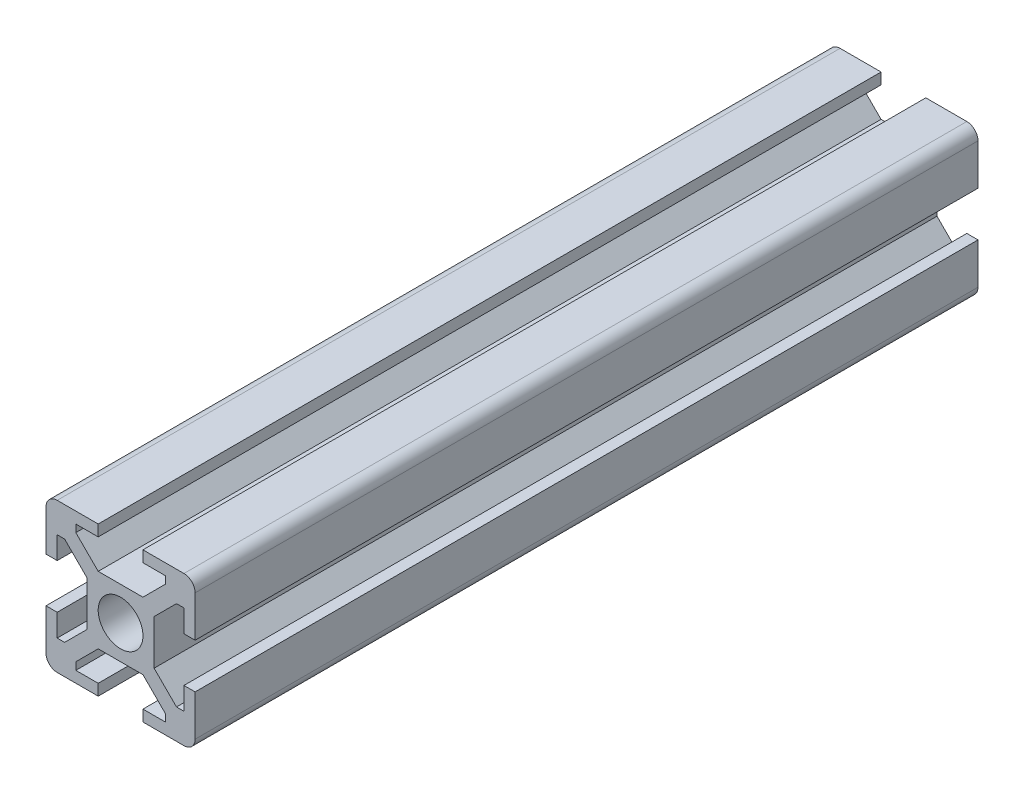
SolidWorks part; units mm, degrees
ref_plane "Plan de face" through (0, 0, 0) normal (0, 0, 1) x (1, 0, 0)
ref_plane "Plan de dessus" through (0, 0, 0) normal (0, 1, 0) x (1, 0, 0)
ref_plane "Plan de droite" through (0, 0, 0) normal (1, 0, 0) x (0, 0, -1)
sketch "Esquisse1" plane through (0, 0, 0) normal (0, 0, 1) x (1, 0, 0)
  line L0 (-10, 10) -> (10, -10) construction
  line L1 (-10, 10) -> (10, 10)
  line L2 (-10, 10) -> (-10, -10)
  line L3 (-10, -10) -> (10, -10)
  line L4 (10, 10) -> (10, -10)
  dimension "D1" = 20
extrude "Extrusion1" add sketch "Esquisse1" along normal mid plane 105
fillet "Congé1" radius 1.5 4 edges at (-10, -10, 0) (10, -10, 0) (-10, 10, 0) (10, 10, 0)
sketch "Esquisse2" plane through (0, 0, -52.5) normal (0, 0, -1) x (-1, 0, 0)
  line L0 (-10, 3) -> (-10, -3)
  line L1 (-10, -8.5) -> (-10, 8.5) construction
  line L2 (-10, -3) -> (-8.5, -3)
  line L3 (-8.5, -3) -> (-8.5, -6)
  line L4 (-8.5, 6) -> (-7.5, 6)
  line L5 (-4.5, -3) -> (-4.5, 3)
  line L6 (-7.5, 6) -> (-4.5, 3)
  line L7 (-8.5, 6) -> (-8.5, 3)
  line L8 (-8.5, 3) -> (-10, 3)
  line L9 (0, 0) -> (-10, 0) construction
  line L10 (-8.5, -6) -> (-7.5, -6)
  line L11 (-7.5, -6) -> (-4.5, -3)
  point P4 (-10, 0)
  dimension "D1" = 6
  dimension "D2" = 12
  dimension "D3" = 1.5
  dimension "D4" = 5.5
  dimension "D5" = 135
extrude "Enlèv. mat.-Extru.1" cut sketch "Esquisse2" against normal through all
ref_axis "Axe1" through (0, 0, 9.3338) along (0, 0, -1)
pattern_circular "Répétition circulaire1" count 4 over 360 about axis through (0, 0, 9.3338) along (0, 0, -1) of "Enlèv. mat.-Extru.1"
hole_wizard "Trou taraudé M6x1.01" positions "Esquisse4" profile "Esquisse5" tap size "M6x1.0" standard "Ansi Métrique"
sketch "Esquisse4" plane through (0, 0, -52.5) normal (0, 0, -1) x (-1, 0, 0)
  point P0 (0, 0)
sketch "Esquisse5" plane through (0, 0, -52.5) normal (1, 0, 0) x (0, 1, 0)
  line L0 (0, 0) -> (0, 31.5022)
  line L1 (0, 31.5022) -> (2.5, 30)
  line L2 (2.5, 30) -> (2.5, 24)
  line L3 (2.5, 24) -> (3, 24)
  line L4 (3, 24) -> (3, 0)
  line L5 (3, 0) -> (0, 0)
  line L10 (0, 31.5022) -> (-2.5, 30) construction
  line L11 (0, -6.35) -> (0, 107.95) construction
  dimension "Diamètre du trou pour taraudage" = 5
  dimension "Profondeur du trou pour taraudage" = 30
  dimension "Diamètre principal du filetage" = 6
  dimension "Profondeur du filetage" = 24
  dimension "Angle de pointe" = 118
mirror "Symétrie1" about plane through (0, 0, 0) normal (0, 0, 1) of "Trou taraudé M6x1.01"
